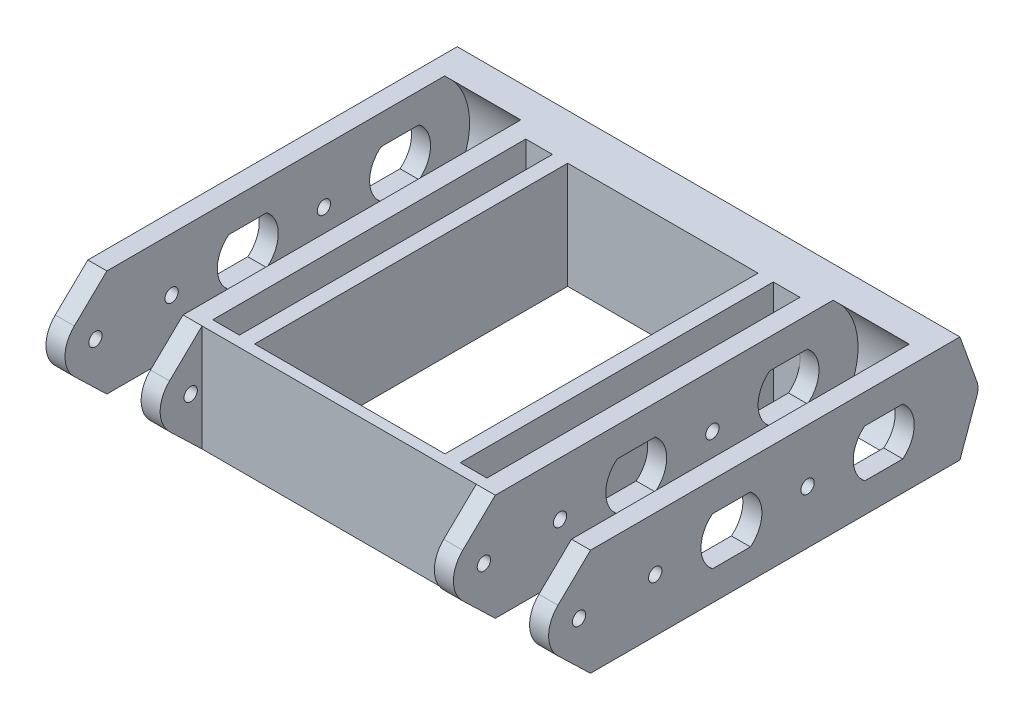
SolidWorks part; units mm, degrees
note: The reader was unsure of these and kept them because the rebuilt part matched: shared geometry of "Sketch1<13>".
material "ABS"
ref_plane "Front Plane" through (0, 0, 0) normal (0, 0, 1) x (1, 0, 0)
ref_plane "Top Plane" through (0, 0, 0) normal (0, 1, 0) x (1, 0, 0)
ref_plane "Right Plane" through (0, 0, 0) normal (1, 0, 0) x (0, 0, -1)
sketch "Sketch1" plane through (0, 0, 0) normal (1, 0, 0) x (0, 0, -1)
  line L0 (0, 0) -> (40, 0) construction
  line L1 (0, 0) -> (-40, 0) construction
  line L2 (44.9937, 6.25) -> (35.0063, 6.25)
  line L3 (44.9937, -6.25) -> (35.0063, -6.25)
  line L4 (4.9937, -6.25) -> (-4.9937, -6.25)
  line L5 (4.9937, 6.25) -> (-4.9937, 6.25)
  line L8 (60, 14) -> (64.4682, 1.6116)
  line L9 (64.4682, -1.6116) -> (60, -14)
  line L11 (-37, 14) -> (-45.5509, 5.7609)
  line L12 (-37, 14) -> (60, 14)
  line L14 (-37, -14) -> (60, -14)
  line L17 (-37, -14) -> (-45.5509, -5.7609)
  line L20 (40, 0) -> (80, 0) construction
  circle A0 centre (20, 0) radius 1.75
  arc A1 (-4.9937, 6.25) -> (-4.9937, -6.25) centre (0, 0) ccw
  arc A2 (35.0063, 6.25) -> (35.0063, -6.25) centre (40, 0) ccw
  circle A3 centre (-20, 0) radius 1.75
  circle A4 centre (-40, 0) radius 1.75
  circle A5 centre (0, 0) radius 17 construction
  circle A6 centre (40, 0) radius 17 construction
  circle A7 centre (-20, 0) radius 8.5
  arc A8 (44.9937, -6.25) -> (44.9937, 6.25) centre (40, 0) ccw
  arc A9 (4.9937, -6.25) -> (4.9937, 6.25) centre (0, 0) ccw
  circle A10 centre (20, 0) radius 8.5
  circle A11 centre (-40, 0) radius 17 construction
  circle A12 centre (60, 0) radius 1.75
  arc A13 (64.4682, 1.6116) -> (64.4682, -1.6116) centre (60, 0) cw
  arc A14 (-45.5509, -5.7609) -> (-45.5509, 5.7609) centre (-40, 0) cw
  point P23 (-47.2577, -5.4522)
  point P26 (-45.6196, 6.25)
  point P33 (0, 0)
  dimension "D1" = 16
  dimension "D2" = 3.5
  dimension "D3" = 40
  dimension "D5" = 12.5
  dimension "D4" = 3
  dimension "D7" = 8
  dimension "D8" = 28
  dimension "D9" = 3.5
  dimension "D10" = 3
  dimension "D12" = 34
  dimension "D6" = 17
extrude "Boss-Extrude1" add sketch "Sketch1" along normal mid plane 132
sketch "Sketch4" plane through (66, 0, 0) normal (1, 0, 0) x (0, 0, -1)
  line L7 (64.4682, 1.6116) -> (60, 14)
  line L8 (60, 14) -> (-37, 14)
  line L9 (-37, 14) -> (-45.5509, 5.7609)
  line L11 (-45.5509, -5.7609) -> (-37, -14)
  line L12 (-37, -14) -> (60, -14)
  line L13 (60, -14) -> (64.4682, -1.6116)
  line L14 (64.4682, 1.6116) -> (60, 14)
  line L15 (60, 14) -> (-37, 14)
  line L16 (-37, 14) -> (-45.5509, 5.7609)
  line L18 (-45.5509, -5.7609) -> (-37, -14)
  line L19 (-37, -14) -> (60, -14)
  line L20 (60, -14) -> (64.4682, -1.6116)
  circle A0 centre (60, 0) radius 1.75 construction
  arc A1 (64.4682, -1.6116) -> (64.4682, 1.6116) centre (60, 0) ccw
  arc A2 (64.4682, -1.6116) -> (64.4682, 1.6116) centre (60, 0) ccw
  arc A4 (51.7074, -14) -> (51.7074, 14) centre (40, 0) ccw
  arc A7 (-45.5509, 5.7609) -> (-45.5509, -5.7609) centre (-40, 0) ccw
  arc A8 (-45.5509, 5.7609) -> (-45.5509, -5.7609) centre (-40, 0) ccw
  line M12 (-37, 14) -> (-45.5509, 5.7609)
  arc M13 (-45.5509, 5.7609) -> (-45.5509, -5.7609) centre (-40, 0) ccw
  line M14 (-45.5509, -5.7609) -> (-37, -14)
  line M15 (-37, -14) -> (60, -14)
  dimension "D1" = 0
extrude "Cut-Extrude3" cut sketch "Sketch4" against normal blind 20 from offset 5 contours A4 L15 M15 M12 M13 M14 offset against normal yes
sketch "Sketch5" plane through (41, 0, 0) normal (1, 0, 0) x (0, 0, -1)
  line L0 (-37, -14) -> (60, -14) construction
  line L3 (48, -14) -> (-34.2, -14)
  line L4 (48, -14) -> (48, 14)
  line L5 (48, 14) -> (-34.2, 14)
  line L6 (-34.2, -14) -> (-34.2, 14)
  line L7 (-37, 14) -> (60, 14) construction
  arc A1 (44.9937, -6.25) -> (44.9937, 6.25) centre (40, 0) ccw construction
  dimension "D1" = 2.8
extrude "Cut-Extrude4" cut sketch "Sketch5" against normal blind 7 from offset 5 offset against normal yes
extrude "Cut-Extrude5" cut sketch "Sketch1<13>" against normal up to surface (37 mm away) from vertex contours L4 A9 L5 A1 | L3 A8 L2 A2 | A3 | A0 | A4
sketch "Sketch1<13>" plane through (0, 0, 0) normal (1, 0, 0) x (0, 0, -1) same geometry as "Sketch1"
mirror "Mirror2" about plane through (0, 0, 0) normal (1, 0, 0) of "Cut-Extrude5", "Cut-Extrude4", "Cut-Extrude3"
sketch "Sketch7" plane through (0, 14, 0) normal (0, 1, 0) x (1, 0, 0)
  line L0 (41, -37) -> (-41, -37) construction
  line L1 (-36, -37) -> (36, -37)
  line L2 (-36, -37) -> (-36, -48)
  line L3 (-36, -48) -> (36, -48)
  line L4 (36, -37) -> (36, -48)
  line L6 (36, 48) -> (36, -34.2) construction
  line L7 (-36, 48) -> (-36, -34.2) construction
  line L8 (-41, -48) -> (41, -48) construction
  point P6 (36, -48)
extrude "Cut-Extrude7" cut sketch "Sketch7" against normal through all
sketch "Sketch8" plane through (0, 14, 0) normal (0, 1, 0) x (1, 0, 0)
  line L0 (-29, 48) -> (-29, -34.2) construction
  line L1 (-25, -34.2) -> (25, -34.2)
  line L2 (-25, -34.2) -> (-25, 48)
  line L3 (-25, 48) -> (25, 48)
  line L4 (25, -34.2) -> (25, 48)
  line L5 (-29, -34.2) -> (-36, -34.2) construction
  line L6 (29, 48) -> (36, 48) construction
  point P6 (0, 48)
  point P10 (25, 47.4871)
  dimension "D1" = 4
extrude "Cut-Extrude8" cut sketch "Sketch8" against normal through all
